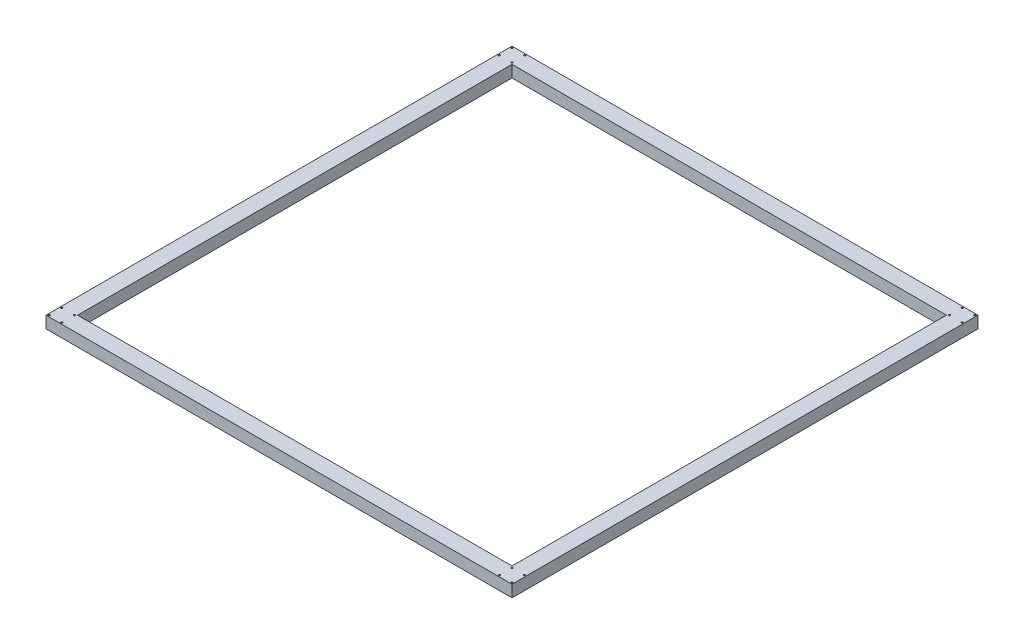
SolidWorks part; units mm, degrees
material "Concreto"
ref_plane "Plano frontal" through (0, 0, 0) normal (0, 0, 1) x (1, 0, 0)
ref_plane "Plano superior" through (0, 0, 0) normal (0, 1, 0) x (1, 0, 0)
ref_plane "Plano direito" through (0, 0, 0) normal (1, 0, 0) x (0, 0, -1)
sketch "Esboço1" plane through (0, 0, 0) normal (0, 1, 0) x (1, 0, 0)
  line L5 (-2750, 2750) -> (2750, 2750)
  line L6 (-2750, 2750) -> (-2750, -2750)
  line L11 (-2750, -2750) -> (2750, -2750)
  line L12 (2750, 2750) -> (2750, -2750)
  line L13 (-2750, 2750) -> (2750, -2750) construction
  line L14 (-2750, -2750) -> (2750, 2750) construction
  line L15 (-2950, 2950) -> (2950, 2950)
  line L16 (-2950, 2950) -> (-2950, -2950)
  line L17 (-2950, -2950) -> (2950, -2950)
  line L18 (2950, 2950) -> (2950, -2950)
  line L19 (-2950, 2950) -> (2950, -2950) construction
  line L20 (-2950, -2950) -> (2950, 2950) construction
  circle A0 centre (-2770, 2770) radius 10 construction
  circle A1 centre (-2930, 2770) radius 10 construction
  circle A2 centre (-2930, 2930) radius 10 construction
  circle A3 centre (-2770, 2930) radius 10 construction
  circle A4 centre (2930, 2770) radius 10 construction
  circle A5 centre (2930, 2930) radius 10 construction
  circle A6 centre (2770, 2770) radius 10 construction
  circle A7 centre (2770, 2930) radius 10 construction
  circle A8 centre (2930, -2930) radius 10 construction
  circle A9 centre (2770, -2930) radius 10 construction
  circle A10 centre (2930, -2770) radius 10 construction
  circle A11 centre (2770, -2770) radius 10 construction
  circle A12 centre (-2770, -2930) radius 10 construction
  circle A13 centre (-2930, -2930) radius 10 construction
  circle A14 centre (-2770, -2770) radius 10 construction
  circle A15 centre (-2930, -2770) radius 10 construction
  circle A16 centre (-2770, 2770) radius 10
  circle A17 centre (-2930, 2770) radius 10
  circle A18 centre (-2930, 2930) radius 10
  circle A19 centre (-2770, 2930) radius 10
  circle A20 centre (2930, 2770) radius 10
  circle A21 centre (2930, 2930) radius 10
  circle A22 centre (2770, 2770) radius 10
  circle A23 centre (2770, 2930) radius 10
  circle A24 centre (2930, -2930) radius 10
  circle A25 centre (2770, -2930) radius 10
  circle A26 centre (2930, -2770) radius 10
  circle A27 centre (2770, -2770) radius 10
  circle A28 centre (-2770, -2930) radius 10
  circle A29 centre (-2930, -2930) radius 10
  circle A30 centre (-2770, -2770) radius 10
  circle A31 centre (-2930, -2770) radius 10
  point P0 (0, 0)
  point P6 (0, 0)
  dimension "D1" = 5500
  dimension "D2" = 5500
  dimension "D3" = 200
  dimension "D4" = 200
extrude "Ressalto-extrusão1" add sketch "Esboço1" along normal blind 150
